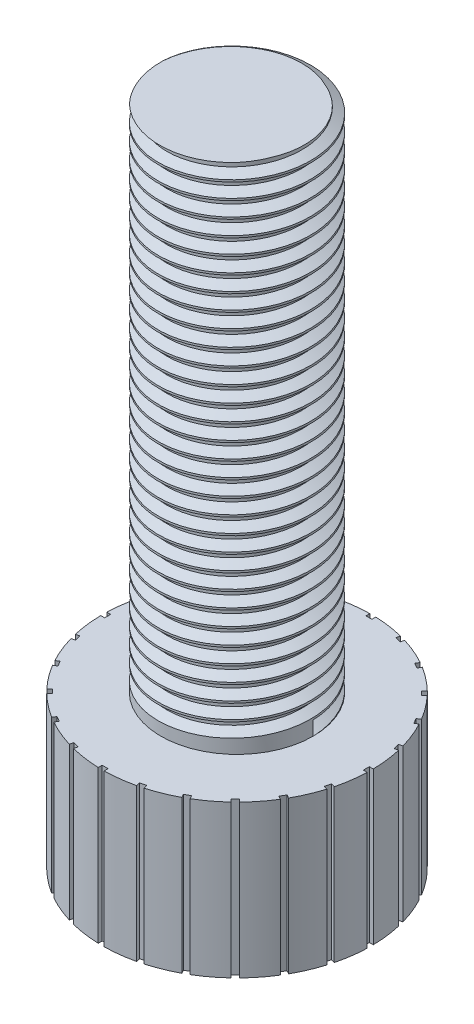
SolidWorks part; units mm, degrees
ref_plane "前视基准面" through (0, 0, 0) normal (0, 0, 1) x (1, 0, 0)
ref_plane "上视基准面" through (0, 0, 0) normal (0, 1, 0) x (1, 0, 0)
ref_plane "右视基准面" through (0, 0, 0) normal (1, 0, 0) x (0, 0, -1)
sketch "草图1" plane through (0, 0, 0) normal (0, 1, 0) x (1, 0, 0)
  circle A0 centre (0, 0) radius 2.65
  dimension "D1" = 5.3
extrude "凸台-拉伸1" add sketch "草图1" along normal blind 3
sketch "草图2" plane through (0, 3, 0) normal (0, 1, 0) x (1, 0, 0)
  circle A0 centre (0, 0) radius 1.5
  dimension "D1" = 3
extrude "凸台-拉伸2" add sketch "草图2" along normal blind 10
thread "螺纹线1" pitch 0.3175 profile "螺纹线轮廓2" start angle 0, offset 0, length 15, pitch 0.3175, diameter 3
ref_plane "基准面2" through (1.5, 3, 0) normal (0, 0, 1) x (1, 0, 0)
sketch "螺纹线轮廓2" plane through (1.5, 3, 0) normal (0, 0, 1) x (1, 0, 0)
  line L0 (0, 0) -> (0, 0.3175) construction
  line L11 (0, 0) -> (0, 0.2778)
  line L12 (0, 0.2778) -> (-0.1719, 0.1786)
  line L13 (-0.1719, 0.1786) -> (-0.1719, 0.0992)
  line L15 (-0.1719, 0.0992) -> (0, 0)
  line L17 (-0.1719, 0.1389) -> (0, 0.1389) construction
  point P2 (0, 0)
  dimension "Pitch" = 0.3175
  dimension "Profile_Angle" = 60
  dimension "Profile_Land" = 0.0794
  dimension "Profile_Height" = 0.1719
sketch "草图7" plane through (0, 0, 0) normal (0, -1, 0) x (-1, 0, 0)
  line L1 (-1.4434, 0) -> (-0.7217, -1.25)
  line L2 (-0.7217, -1.25) -> (0.7217, -1.25)
  line L3 (0.7217, -1.25) -> (1.4434, 0)
  line L4 (1.4434, 0) -> (0.7217, 1.25)
  line L5 (0.7217, 1.25) -> (-0.7217, 1.25)
  line L6 (-0.7217, 1.25) -> (-1.4434, 0)
  circle A0 centre (0, 0) radius 1.25 construction
  dimension "D1" = 2.5
extrude "切除-拉伸1" cut sketch "草图7" against normal blind 1
sketch "草图8" plane through (0, 0, 0) normal (0, -1, 0) x (-1, 0, 0)
  line L1 (-2.7531, -0.0842) -> (-2.5724, -0.0842)
  line L2 (-2.7531, -0.0842) -> (-2.7531, 0.0339)
  line L3 (-2.7531, 0.0339) -> (-2.5724, 0.0339)
  line L4 (-2.5724, -0.0842) -> (-2.5724, 0.0339)
extrude "切除-拉伸2" cut sketch "草图8" against normal blind 5
sketch "草图9" plane through (0, 0, 0) normal (0, 0, 1) x (1, 0, 0)
  line L0 (0, 0) -> (0, 2.7041) construction
pattern_circular "阵列(圆周)1" count 24 over 360 about axis through (0, 0, 0) along (0, 1, 0) of "切除-拉伸2"
